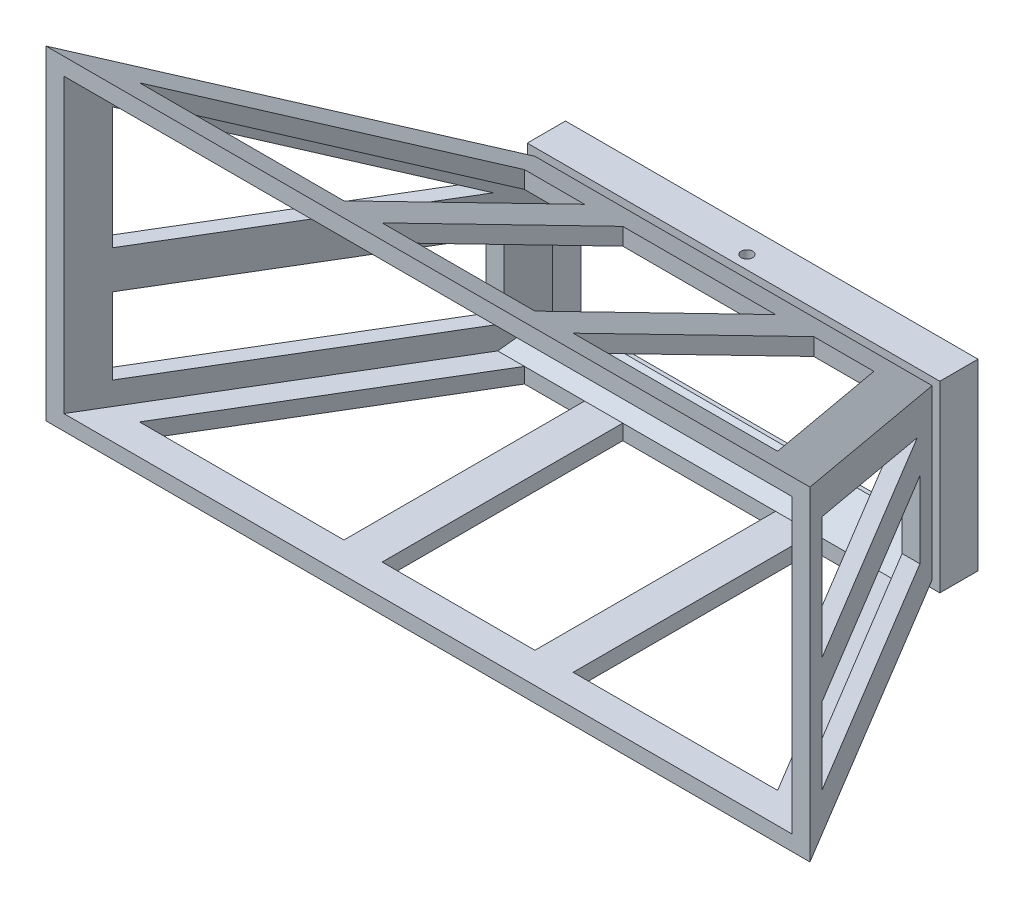
SolidWorks part; units mm, degrees
ref_plane "前视基准面" through (0, 0, 0) normal (0, 0, 1) x (1, 0, 0)
ref_plane "上视基准面" through (0, 0, 0) normal (0, 1, 0) x (1, 0, 0)
ref_plane "右视基准面" through (0, 0, 0) normal (1, 0, 0) x (0, 0, -1)
sketch "草图1" plane through (0, 0, 0) normal (0, 0, 1) x (1, 0, 0)
  line L0 (54, 24) -> (-54, 24)
  line L1 (50, -20) -> (-50, -20)
  line L2 (50, -20) -> (50, 20)
  line L3 (50, 20) -> (-50, 20)
  line L4 (-50, -20) -> (-50, 20)
  line L5 (50, -20) -> (-50, 20) construction
  line L6 (50, 20) -> (-50, -20) construction
  line L7 (-54, -24) -> (-54, 24)
  line L8 (54, -24) -> (-54, -24)
  line L9 (54, -24) -> (54, 24)
  point P0 (0, 0)
  dimension "D1" = 100
  dimension "D2" = 40
  dimension "D3" = 4
extrude "凸台-拉伸1" add sketch "草图1" along normal blind 10
sketch "草图2" plane through (0, 0, 10) normal (0, 0, 1) x (1, 0, 0)
  line L0 (52, 22) -> (-52, 22)
  line L1 (50, 20) -> (-50, 20) construction
  line L2 (-50, 20) -> (-50, -20) construction
  line L3 (-50, -20) -> (50, -20) construction
  line L7 (-52, -22) -> (-52, 22)
  line L8 (52, -22) -> (-52, -22)
  line L10 (52, -22) -> (52, 22)
  dimension "D1" = 2
  dimension "D2" = 2
  dimension "D3" = 2
ref_plane "基准面1" through (0, 0, 90) normal (0, 0, 1) x (1, 0, 0)
sketch "草图5" plane through (0, 0, 90) normal (0, 0, 1) x (1, 0, 0)
  line L0 (52, -22) -> (-52, -22) construction
  line L2 (-100, -22) -> (100, -22)
  line L3 (-100, -22) -> (-100, 63)
  line L4 (-100, 63) -> (100, 63)
  line L5 (100, -22) -> (100, 63)
  line L6 (-100, -22) -> (100, 63) construction
  line L7 (-100, 63) -> (100, -22) construction
  point P4 (0, 18.5)
  point P7 (0, 20.5)
  dimension "D1" = 200
  dimension "D2" = 85
loft "放样3" add profiles "草图5", "草图2" connector at (-100, -22, 90) connector at (-52, -22, 10)
shell "抽壳2" thickness 4 removed face at (0, 0, 10) removed face at (0, 20.5, 90)
sketch "草图6" plane through (0, -24, 0) normal (0, -1, 0) x (1, 0, 0)
  line L0 (-54, 10) -> (54, 10) construction
  line L1 (20, 19) -> (-20, 19)
  line L2 (20, 19) -> (20, 82)
  line L3 (20, 82) -> (-20, 82)
  line L4 (-20, 19) -> (-20, 82)
  line L5 (20, 19) -> (-20, 82) construction
  line L6 (20, 82) -> (-20, 19) construction
  line L7 (26.4, 90) -> (-26.4, 90) construction
  line L8 (0, 63.8082) -> (0, 75.2959) construction
  line L9 (30, 19) -> (30, 82)
  line L10 (30, 82) -> (83.5381, 82)
  line L11 (83.5381, 82) -> (45.7381, 19)
  line L12 (45.7381, 19) -> (30, 19)
  line L13 (100, 90) -> (52, 10) construction
  line L14 (-45.7381, 19) -> (-30, 19)
  line L15 (-83.5381, 82) -> (-45.7381, 19)
  line L16 (-30, 82) -> (-83.5381, 82)
  line L17 (-30, 19) -> (-30, 82)
  point P0 (0, 50.5)
  dimension "D1" = 9
  dimension "D2" = 8
  dimension "D3" = 40
  dimension "D4" = 8
  dimension "D5" = 9
  dimension "D6" = 10
  dimension "D7" = 10
extrude "切除-拉伸1" cut sketch "草图6" against normal blind 102
sketch "草图7" plane through (-54, 0, 0) normal (-1, 0, 0) x (0, 0, 1)
  line L0 (18, -12) -> (82, -12)
  line L1 (82, -12) -> (82, 8)
  line L2 (82, 8) -> (18, 8)
  line L3 (18, 8) -> (18, -16.2657)
  line L4 (18, 17.1106) -> (82, 49.9106)
  line L5 (82, 49.9106) -> (82, 18)
  line L6 (82, 18) -> (18, 18)
  line L7 (18, 18) -> (18, 17.1106)
  line L8 (90, 63) -> (90, -22) construction
  line L9 (10, 22) -> (10, -22) construction
  line L10 (10, 24) -> (10, -24) construction
  line L11 (90, 63) -> (10, 22) construction
  line L12 (90, -22) -> (10, -22) construction
  dimension "D1" = 8
  dimension "D2" = 8
  dimension "D3" = 8
  dimension "D4" = 8
  dimension "D5" = 10
  dimension "D6" = 8
  dimension "D7" = 10
  dimension "D8" = 20
extrude "切除-拉伸2" cut sketch "草图7" against normal mid plane 398 contours L2 L3 L0 L1 | L6 L5 L4 | L4 L5 L6 L7 region at (-54, -2, 50) region at (-54, 28.6369, 61.2452)
sketch "草图8" plane through (0, 24, 0) normal (0, 1, 0) x (1, 0, 0)
  line L0 (54, 0) -> (-54, 0) construction
  circle A0 centre (0, -6.5) radius 1.5
  dimension "D1" = 3
  dimension "D2" = 6.5
extrude "切除-拉伸3" cut sketch "草图8" against normal blind 139
sketch "草图10" plane through (0, -18, 0) normal (0, 1, 0) x (1, 0, 0)
  line L0 (-52.7352, -19) -> (52.7352, -19)
  line L1 (-95.3352, -90) -> (-47.3352, -10) construction
  line L2 (95.3352, -90) -> (47.3352, -10) construction
  line L3 (-50, -10) -> (50, -10) construction
  dimension "D1" = 9
sketch "草图11" plane through (0, 0, 10) normal (0, 0, -1) x (-1, 0, 0)
  line L0 (-47.3352, 17.5053) -> (-47.3352, -18) construction
  line L1 (47.3352, -18) -> (-47.3352, -18)
  line L2 (47.3352, -18) -> (47.3352, -11)
  line L3 (47.3352, -11) -> (-47.3352, -11)
  line L4 (-47.3352, -18) -> (-47.3352, -11)
  line L5 (47.3352, -18) -> (-47.3352, -11) construction
  line L6 (47.3352, -11) -> (-47.3352, -18) construction
  point P4 (0, -14.5)
  dimension "D1" = 7
sketch "草图12" plane through (-30.3936, 0, -18.2361) normal (0.8575, 0, 0.5145) x (0.5145, 0, -0.8575)
  line L0 (-32.9287, -11) -> (-43.4244, -18)
  line L1 (-43.4244, -18) -> (-32.9287, -18)
  line L2 (-32.9287, -18) -> (-32.9287, -11)
sketch "草图13" plane through (30.3936, 0, -18.2361) normal (-0.8575, 0, 0.5145) x (0.5145, 0, 0.8575)
  line L0 (32.9287, -11) -> (43.4244, -18)
  line L1 (43.4244, -18) -> (32.9287, -18)
  line L2 (32.9287, -18) -> (32.9287, -11)
loft "放样5" add profiles "草图13", "草图12" connector at (47.3352, -11, 10) connector at (-47.3352, -11, 10)
